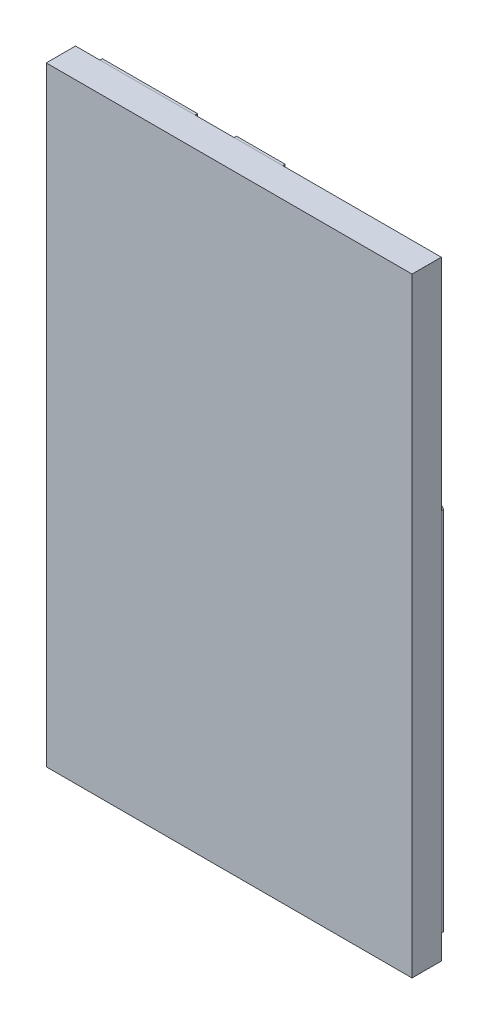
SolidWorks part; units mm, degrees
ref_plane "Front" through (0, 0, 0) normal (0, 0, 1) x (1, 0, 0)
ref_plane "Top" through (0, 0, 0) normal (0, 1, 0) x (1, 0, 0)
ref_plane "Right" through (0, 0, 0) normal (1, 0, 0) x (0, 0, -1)
sketch "Sketch1" plane through (0, 0, 0) normal (0, 0, 1) x (1, 0, 0)
  line L1 (0, 0) -> (15, 0)
  line L2 (0, 0) -> (0, -25)
  line L3 (0, -25) -> (15, -25)
  line L4 (15, 0) -> (15, -25)
  dimension "D1" = 15
  dimension "D2" = 25
extrude "Boss-Extrude1" add sketch "Sketch1" along normal blind 1.2
sketch "Sketch2" plane through (0, 0, 0) normal (0, 0, -1) x (-1, 0, 0)
  line L6 (-7.5, -25) -> (-7.5, 0) construction
  line L27 (0, -25) -> (-15, -25) construction
  line L28 (-15, 0) -> (0, 0) construction
  line L66 (-6.5, -17) -> (-11.4, -17)
  line L68 (-4.9, 0) -> (0, 0)
  line L69 (-4.9, 0) -> (-4.9, -2)
  line L70 (-4.9, -2) -> (-2, -2)
  line L72 (-8.5, 0) -> (-6.5, 0)
  line L73 (-3.6, -10) -> (-7.5, -10)
  line L74 (-3.6, -10) -> (-3.6, -8)
  line L75 (-3.6, -8) -> (-6.5, -8)
  line L76 (-11, -10) -> (-11, -8)
  line L77 (-8.5, 0) -> (-8.5, -8)
  line L79 (-6.5, 0) -> (-6.5, -8)
  line L83 (-2, -2) -> (-2, -17)
  line L84 (-6.5, -25) -> (-4.5, -25)
  line L85 (-6.5, -25) -> (-6.5, -17)
  line L87 (-4.5, -25) -> (-4.5, -17)
  line L88 (0, -17) -> (-2, -17)
  line L91 (-11.4, -17) -> (-11.4, -15)
  line L93 (-8.5, -25) -> (-8.5, -23)
  line L94 (-8.5, -23) -> (-13, -23)
  line L97 (-15, -25) -> (-15, -8)
  line L99 (-13, -23) -> (-13, -8)
  line L100 (-15, -8) -> (-13, -8)
  line L104 (-4, -15) -> (-4, -17)
  line L106 (-4, -17) -> (-4.5, -17)
  line L107 (-4, -15) -> (-11.4, -15)
  line L108 (-8.5, -8) -> (-11, -8)
  line L109 (-7.5, -10) -> (-11, -10)
  line L110 (0, -17) -> (0, 0)
  line L111 (-15, -25) -> (-8.5, -25)
  line L112 (0, 0) -> (0, -25) construction
  line L113 (-15, -25) -> (-15, 0) construction
  dimension "D1" = 2.6
  dimension "D2" = 2
  dimension "D3" = 2
  dimension "D4" = 1.6
  dimension "D5" = 2
  dimension "D6" = 17
  dimension "D7" = 17
  dimension "D8" = 2
  dimension "D10" = 1
  dimension "D11" = 1
  dimension "D14" = 1.6
extrude "Boss-Extrude2" add sketch "Sketch2" along normal blind 0.1 separate body
sketch "Sketch3" plane through (0, 0, 0) normal (0, 0, -1) x (-1, 0, 0)
  line L0 (-11.4, -17) -> (-6.5, -17) construction
  line L1 (-8.5, -23) -> (-10.5, -23)
  line L2 (-8.5, -23) -> (-8.5, -19)
  line L3 (-8.5, -19) -> (-10.5, -19)
  line L4 (-10.5, -23) -> (-10.5, -19)
  dimension "D1" = 2
  dimension "D2" = 2
extrude "Boss-Extrude3" add sketch "Sketch3" along normal up to surface (0.1 mm away) up to face at (12.1667, -18.6667, -0.1)
chamfer "Chamfer5" distance 1 angle 45 4 edges at (15, -25, -0.05) (13, -23, -0.05) (10.5, -23, -0.05) (15, -8, -0.05)
chamfer "Chamfer6" distance 1 angle 45 2 edges at (6.5, -17, -0.05) (4.5, -17, -0.05)
chamfer "Chamfer7" distance 1 angle 45 3 edges at (0, 0, -0.05) (2, -2, -0.05) (0, -17, -0.05)
chamfer "Chamfer8" distance 1 angle 45 2 edges at (8.5, -8, -0.05) (6.5, -8, -0.05)
